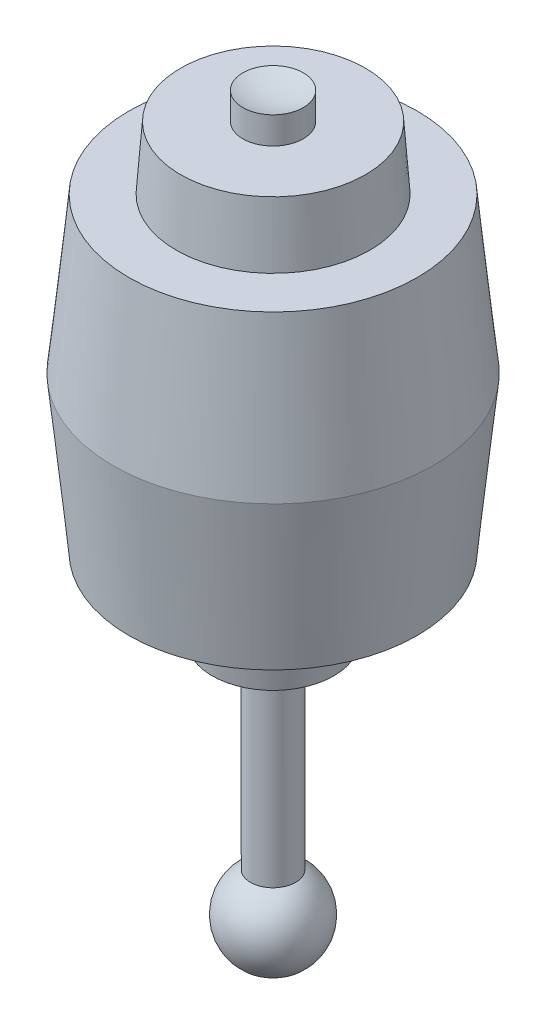
SolidWorks part; units mm, degrees
ref_plane "Спереди" through (0, 0, 0) normal (0, 0, 1) x (1, 0, 0)
ref_plane "Сверху" through (0, 0, 0) normal (0, 1, 0) x (1, 0, 0)
ref_plane "Справа" through (0, 0, 0) normal (1, 0, 0) x (0, 0, -1)
sketch "Sketch1" plane through (0, 0, 0) normal (0, 0, 1) x (1, 0, 0)
  line L0 (0, -52) -> (0, 117.6024) construction
  line L2 (-2.5, -47.6699) -> (-2.5, -25.7)
  line L3 (-2.5, -25.7) -> (-6.75, -25.7)
  line L4 (-6.75, -25.7) -> (-7.75, -17.2)
  line L5 (-7.75, -17.2) -> (-16, -17.2)
  line L6 (-16, -17.2) -> (-17.75, 0)
  line L7 (-17.75, 0) -> (-16, 17.2)
  line L8 (-16, 17.2) -> (-10.75, 17.2)
  line L9 (-10.75, 17.2) -> (-10.25, 24.2)
  line L10 (-10.25, 24.2) -> (-3.35, 24.2)
  line L11 (-3.35, 24.2) -> (-3.35, 27.2)
  line L12 (0, 26.6222) -> (0, -57)
  arc A0 (-3.35, 27.2) -> (0, 26.6222) centre (0, 36.6222) ccw
  arc A1 (-2.5, -47.6699) -> (0, -57) centre (0, -52) ccw
  dimension "D1" = 6.7
  dimension "D2" = 10
  dimension "D14" = 5
  dimension "D3" = 3
  dimension "D4" = 5
  dimension "D5" = 13.5
  dimension "D6" = 15.5
  dimension "D7" = 35.5
  dimension "D8" = 32
  dimension "D9" = 21.5
  dimension "D10" = 20.5
  dimension "D11" = 34.4
  dimension "D12" = 7
  dimension "D13" = 8.5
  dimension "D15" = 52
revolve "Revolve1" add sketch "Sketch1" angle 360 about L0
ref_axis "Axis1" through (0, 64.0065, 0) along (0, -1, 0)
